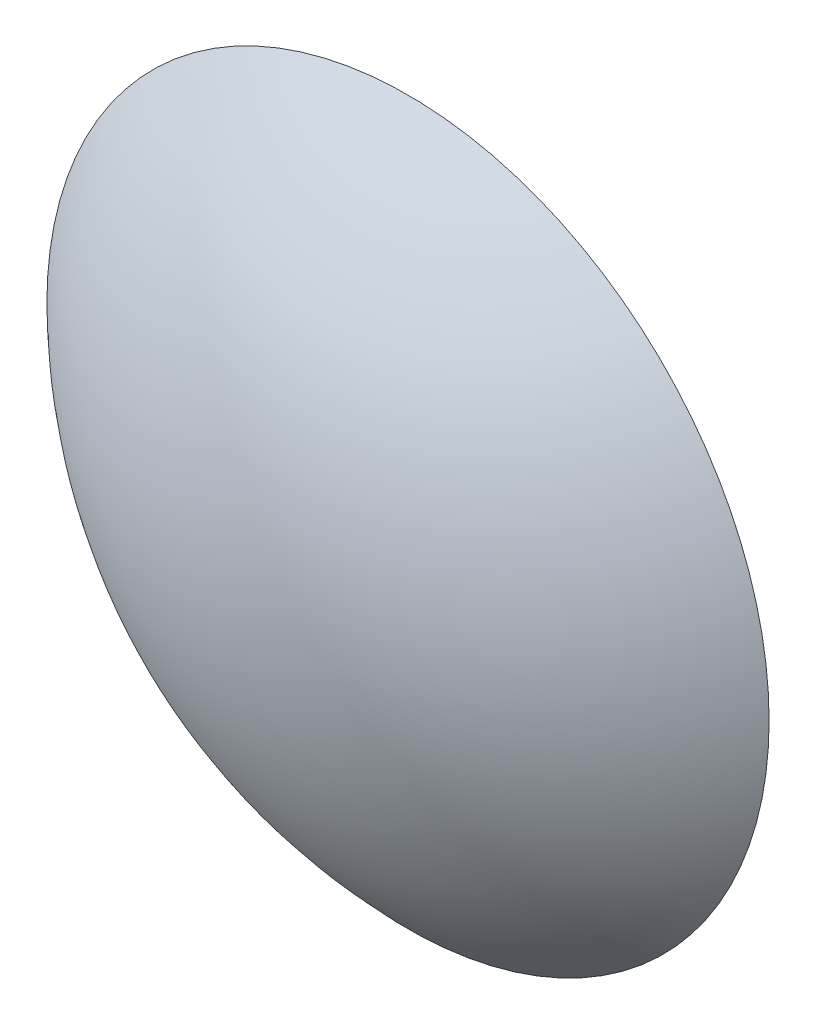
SolidWorks part; units mm, degrees
ref_plane "Front Plane" through (0, 0, 0) normal (0, 0, 1) x (1, 0, 0)
ref_plane "Top Plane" through (0, 0, 0) normal (0, 1, 0) x (1, 0, 0)
ref_plane "Right Plane" through (0, 0, 0) normal (1, 0, 0) x (0, 0, -1)
sketch "Sketch1" plane through (0, 0, 0) normal (0, 1, 0) x (1, 0, 0)
  line L0 (0, -87.5) -> (0, 0)
  line L1 (62.5, -62.5) -> (61.2372, -62.5)
  line L2 (62.5, -62.5) -> (62.5, -61.2372)
  line L3 (62.5, 62.5) -> (61.2372, 62.5)
  line L4 (-62.5, -62.5) -> (-62.5, -61.2372)
  line L5 (62.5, -62.5) -> (61.8718, -61.8718) construction
  line L6 (62.5, 62.5) -> (-62.5, -62.5) construction
  line L7 (0, -62.5) -> (-62.5, -62.5)
  line L8 (-61.8718, 61.8718) -> (-62.5, 62.5) construction
  line L9 (62.5, 61.2372) -> (62.5, 62.5)
  line L10 (-61.2372, 62.5) -> (-62.5, 62.5)
  line L11 (-62.5, 61.2372) -> (-62.5, 62.5)
  arc A0 (61.2372, -62.5) -> (62.5, -61.2372) centre (0, 0) ccw
  arc A1 (62.5, 61.2372) -> (61.2372, 62.5) centre (0, 0) ccw
  arc A2 (-61.2372, 62.5) -> (-62.5, 61.2372) centre (0, 0) ccw
  arc A3 (-62.5, -61.2372) -> (0, -87.5) centre (0, 0) ccw
  arc A4 (-59.6429, -58.4378) -> (0, -83.5) centre (0, 0) ccw
  dimension "D1" = 175
  dimension "D2" = 125
  dimension "D3" = 125
  dimension "D4" = 4
revolve "Revolve1" add sketch "Sketch1" angle 360 about L0
ref_plane "Plane1" through (0, 0, 67.5) normal (0, 0, -1) x (-1, 0, 0)
sketch "Sketch2" plane through (0, 0, 67.5) normal (0, 0, -1) x (-1, 0, 0)
  circle A0 centre (0, 0) radius 50.9
  circle A1 centre (0, 0) radius 46.9
  dimension "D1" = 93.8
  dimension "D2" = 4
extrude "Boss-Extrude1" add sketch "Sketch2" along normal blind 5 and the other way up to surface contours A0 A1 other way up to face at (61.2372, 0, 62.5)
thread "Thread1" pitch 1.5 start angle 0, offset 0, length 7, pitch 2, diameter 93.8
ref_plane "Plane2" through (46.9, 0, 62.5) normal (0, 1, 0) x (1, 0, 0)
sketch "Thread Profile1" plane through (46.9, 0, 62.5) normal (0, 1, 0) x (1, 0, 0)
  line L0 (0, 0) -> (0, 1.5) construction
  line L1 (0, 0) -> (0.8119, 0.4687)
  line L2 (0.8119, 0.4687) -> (0.8119, 0.6562)
  line L3 (0.8119, 0.6562) -> (0, 1.125)
  line L4 (0.8119, 0.5625) -> (0, 0.5625) construction
  line L11 (0, 0) -> (0, 1.125)
  point P2 (0, 0)
  dimension "Pitch" = 1.5
  dimension "Profile_Angle" = 60
  dimension "Profile_Land" = 0.1875
  dimension "Profile_Height" = 0.8119
ref_plane "Plane3" through (0, 0, 87.5) normal (0, 0, 1) x (1, 0, 0)
sketch "Sketch3" plane through (0, -155, 87.5) normal (0, 0, -1) x (-1, 0, 0)
  line L0 (161.623, -220.1397) -> (502.9563, -220.1397) construction
  arc A2 (26.7091, 170.3432) -> (21.2435, 136.8662) centre (10.7145, 155.7699) ccw
  arc A3 (26.7091, 170.3432) -> (21.2435, 136.8662) centre (16.893, 154.7611) ccw
  arc A5 (5.0152, 160.7407) -> (24.4955, 141.0107) centre (16.1365, 152.2393) ccw
  arc A6 (5.0152, 160.7407) -> (24.4955, 141.0107) centre (26.0977, 162.0744) ccw
  arc A7 (29.4819, 141.2227) -> (29.523, 141.3581) centre (-4.0381, 151.4588) ccw
  arc A8 (29.356, 141.2027) -> (29.523, 141.3581) centre (16.893, 154.7611) ccw
  arc A9 (-1.5976, 186.4218) -> (27.5805, 136.3382) centre (-4.0381, 151.4588) ccw
  arc A10 (29.356, 141.2027) -> (29.4819, 141.2227) centre (26.0977, 162.0744) ccw
  arc A12 (13.9385, 180.7526) -> (27.5805, 136.3382) centre (11.7233, 155.7699) ccw
  spline S0 degree 3 poles (-1.5976, 186.4218) (-4.4469, 186.3298) (-8.8632, 183.1088) (-13.7295, 180.8429) (-17.0272, 172.6683) (-15.1342, 175.314) knots 0 0 0 0 0.422368 0.689357 1 1 1 1
  spline S1 degree 3 poles (13.9385, 180.7526) (8.5116, 184.0153) (-2.7824, 183.6312) (-12.0155, 178.3325) (-15.1342, 175.314) knots 0 0 0 0 0.587035 1 1 1 1
extrude "Cut-Extrude1" [suppressed] cut sketch "Sketch3" along normal offset from surface (0.8346 mm away) 0.5 contours A5 A6 | S1 A12 A9 S0 | A3 A2
equation "\"balldia\"=175"
equation "\"D1@Sketch1\"=\"balldia\""
equation "\"sqrside\"=125"
equation "\"D3@Sketch1\"=\"sqrside\""
equation "\"D2@Sketch1\"=\"sqrside\""
